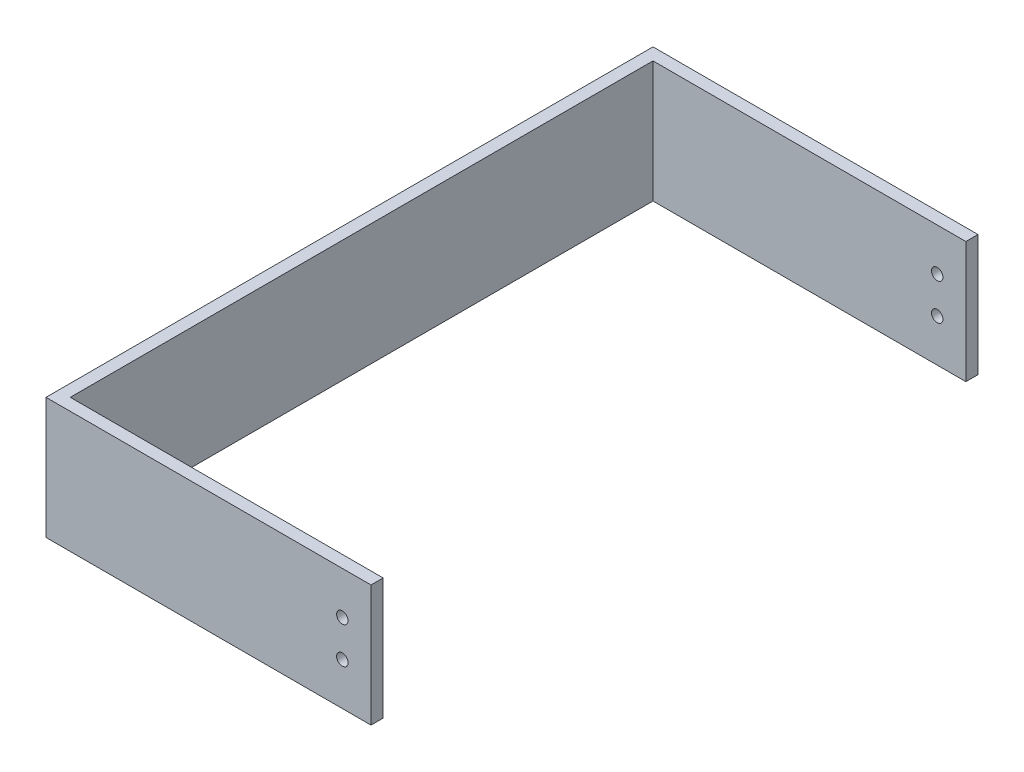
SolidWorks part; units mm, degrees
ref_plane "Front Plane" through (0, 0, 0) normal (0, 0, 1) x (1, 0, 0)
ref_plane "Top Plane" through (0, 0, 0) normal (0, 1, 0) x (1, 0, 0)
ref_plane "Right Plane" through (0, 0, 0) normal (1, 0, 0) x (0, 0, -1)
sketch "Sketch1" plane through (0, 0, 0) normal (0, 1, 0) x (1, 0, 0)
  line L0 (0, 0) -> (-85, 0)
  line L1 (-85, 0) -> (-85, 158.75)
  line L2 (-85, 158.75) -> (0, 158.75)
  line L3 (0, 3.175) -> (-81.825, 3.175)
  line L4 (-81.825, 3.175) -> (-81.825, 155.575)
  line L5 (-81.825, 155.575) -> (0, 155.575)
  line L6 (0, 158.75) -> (0, 155.575)
  line L7 (0, 3.175) -> (0, 0)
  dimension "D1" = 85
  dimension "D2" = 158.75
  dimension "D3" = 0
  dimension "D4" = 3.175
extrude "Boss-Extrude1" add sketch "Sketch1" along normal blind 31.75
sketch "Sketch2" plane through (0, 0, 0) normal (0, 0, 1) x (1, 0, 0)
  line L2 (-85, 31.75) -> (0, 31.75) construction
  line L3 (-85, 0) -> (0, 0) construction
  line L4 (0, 31.75) -> (0, 0) construction
  circle A0 centre (-7.5, 20.6375) radius 1.5
  circle A1 centre (-7.5, 11.1125) radius 1.5
  point P0 (-7.5, 20.6375)
  point P1 (-7.5, 11.1125)
  dimension "D5" = 3
  dimension "D6" = 3
  dimension "D1" = 9.525
  dimension "D2" = 11.1125
  dimension "D3" = 11.1125
  dimension "D4" = 7.5
extrude "Cut-Extrude1" cut sketch "Sketch2" against normal through all contours A1 | A0 region at (-7.5, 11.1125, 0)
